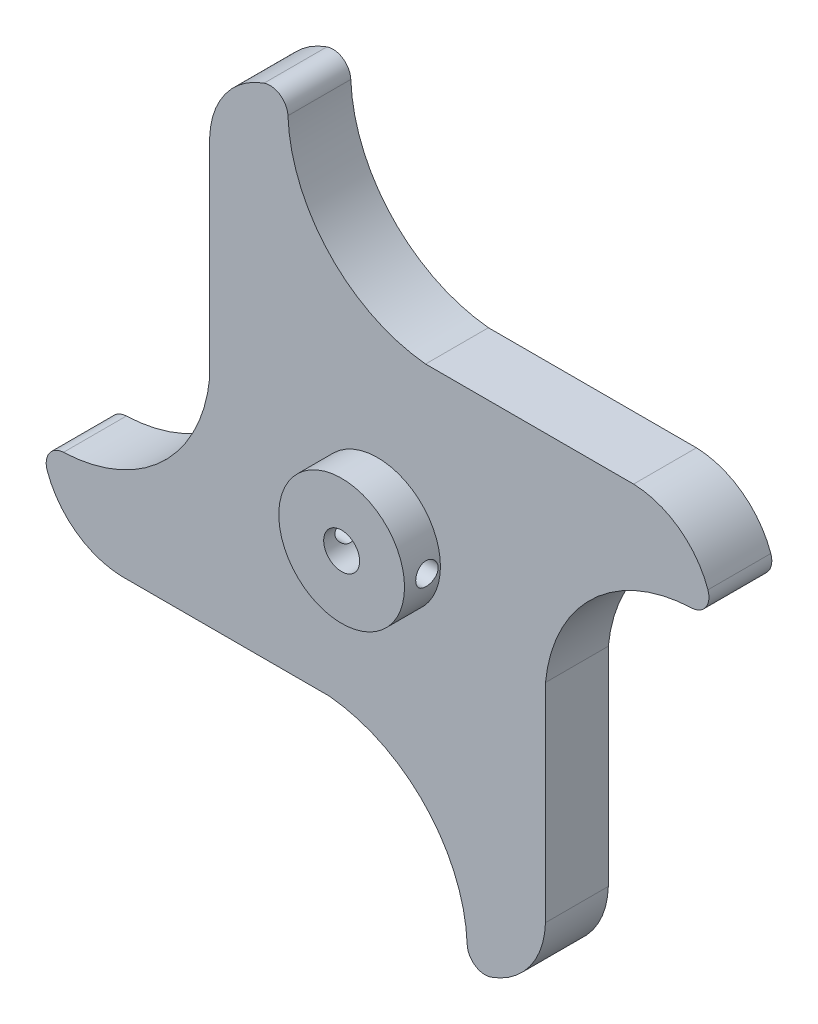
SolidWorks part; units mm, degrees
ref_plane "前视基准面" through (0, 0, 0) normal (0, 0, 1) x (1, 0, 0)
ref_plane "上视基准面" through (0, 0, 0) normal (0, 1, 0) x (1, 0, 0)
ref_plane "右视基准面" through (0, 0, 0) normal (1, 0, 0) x (0, 0, -1)
sketch "草图1" plane through (0, 0, 0) normal (0, 0, 1) x (1, 0, 0)
  circle A0 centre (0, 0) radius 2
  arc A5 (40.8798, 28.7896) -> (28.7896, 40.8798) centre (0, 0) ccw
  arc A7 (-28.7896, 40.8798) -> (-40.8798, 28.7896) centre (0, 0) ccw
  arc A9 (-40.8798, -28.7896) -> (-28.7896, -40.8798) centre (0, 0) ccw
  arc A11 (28.7896, -40.8798) -> (40.8798, -28.7896) centre (0, 0) ccw
  arc A13 (-22.8945, 32.8) -> (22.8945, 32.8) centre (0, 55.6945) ccw
  arc A14 (32.8, 22.8945) -> (32.8, -22.8945) centre (55.6945, 0) ccw
  arc A15 (22.8945, -32.8) -> (-22.8945, -32.8) centre (0, -55.6945) ccw
  arc A16 (-32.8, -22.8945) -> (-32.8, 22.8945) centre (-55.6945, 0) ccw
  arc A21 (-28.7896, 40.8798) -> (28.7896, 40.8798) centre (0, 55.6945) ccw
  arc A22 (40.8798, 28.7896) -> (40.8798, -28.7896) centre (55.6945, 0) ccw
  arc A23 (28.7896, -40.8798) -> (-28.7896, -40.8798) centre (0, -55.6945) ccw
  arc A24 (-40.8798, -28.7896) -> (-40.8798, 28.7896) centre (-55.6945, 0) ccw
  point P13 (45, 0)
  point P16 (0, 0)
  point P45 (0, 0)
  point P47 (0, 0)
  point P63 (0, 0)
  dimension "D1" = 4
  dimension "D3" = 4
  dimension "D4" = 4
extrude "凸台-拉伸1" add sketch "草图1" along normal blind 7 contours A24 A16 A9 A23 A15 A11 A22 A14 A5 A21 A13 A7 A0 region at (35.9294, 27.09, 0)
sketch "草图2" plane through (0, 0, 7) normal (0, 0, 1) x (1, 0, 0)
  line L0 (24.2343, 0) -> (24.2343, 20.8516)
  line L1 (0, -24.2343) -> (-200, -24.2343)
  line L2 (-200, -71.6) -> (3.2733, -71.6)
  line L3 (0, -70) -> (-200, -70)
  line L4 (-200, -23.4) -> (-200, -71.6)
  line L5 (24.2343, 34.0432) -> (24.2343, 20.8516)
  line L6 (-200, -47.5) -> (-20.9464, -47.5)
  line L7 (-200, -23.4) -> (-42.5285, -23.4)
  line L8 (70, 0) -> (70, 107.3223)
  line L9 (24.2343, 34.0432) -> (24.2343, 107.3223)
  line L10 (-35.8334, -17.6395) -> (24.2343, 34.0432)
  line L11 (24.2343, 34.0432) -> (-43.4982, -24.2343)
  line L12 (0, -24.2343) -> (0, 0)
  line L13 (0, 0) -> (0, -24.2343)
  line L14 (-43.4982, -24.2343) -> (-43.4982, -70)
  line L15 (-310.8913, -229.5208) -> (-198.8913, -229.5208)
  line L16 (-254.8913, -229.5208) -> (-251.3913, -229.5208)
  line L17 (-251.3913, -229.5208) -> (-258.3913, -229.5208)
  line L18 (-258.3913, -229.5208) -> (-258.3913, -112.5315)
  line L19 (-258.3913, -112.5315) -> (-251.3913, -112.5315)
  line L20 (-251.3913, -112.5315) -> (-251.3913, -229.5208)
  line L21 (24.2343, 107.3223) -> (70, 107.3223)
  line L22 (47.1172, 107.3223) -> (47.1172, -141.393)
  line L23 (-20.9464, -47.5) -> (114.3656, -47.5)
  line L24 (0, 0) -> (0, -24.2343)
  circle A0 centre (0, -49) radius 21
  circle A1 centre (-310.8913, -229.5208) radius 38.25
  arc A2 (0, -24.2343) -> (24.2343, 0) centre (0, 0) ccw
  arc A3 (0, -70) -> (70, 0) centre (0, 0) ccw
  circle A4 centre (-198.8913, -229.5208) radius 38.25
  circle A5 centre (0, 0) radius 47.1172
  circle A10 centre (-254.8913, -208.9571) radius 21.4063
  point P19 (0, 0)
sketch "草图5" plane through (0, 0, 7) normal (0, 0, 1) x (1, 0, 0)
  line L1 (0, 2.5) -> (-1.7806, 2.5)
  line L2 (-1.7806, 2.5) -> (1.6583, 2.5)
  arc A0 (1.6583, 2.5) -> (-1.6583, 2.5) centre (0, 0) ccw
  circle A1 centre (0, 0) radius 7
  circle M18 centre (0, 0) radius 2
extrude "凸台-拉伸2" add sketch "草图5" along normal blind 4 contours A1 M18 | L1 L2 M18 region at (0, 2.7015, 7) region at (-6.802, 0, 7)
sketch "草图11" plane through (0, 0, 0) normal (1, 0, 0) x (0, 0, -1)
  line L0 (0, 0) -> (-7, 0)
  line L1 (-7, 0) -> (-10, 0)
  circle A0 centre (-8.5, 0) radius 1.25
extrude "切除-拉伸5" cut sketch "草图11" against normal blind 15 and the other way blind 8 contours L1 A0 | L1 A0 region at (0, -0.5305, 8.5) region at (0, 0.5305, 8.5)
sketch "草图13" plane through (0, 0, 0) normal (0, 0, -1) x (-1, 0, 0)
  arc A0 (-25.2436, 31.0284) -> (25.2436, 31.0284) centre (0, 50.6945) ccw
  arc A1 (31.0284, 25.2436) -> (31.0284, -25.2436) centre (50.6945, 0) ccw
  arc A2 (25.2436, -31.0284) -> (-25.2436, -31.0284) centre (0, -50.6945) ccw
  arc A3 (-31.0284, -25.2436) -> (-31.0284, 25.2436) centre (-50.6945, 0) ccw
  arc A4 (-25.2436, 31.0284) -> (-31.0284, 25.2436) centre (0, 0) ccw
  circle A5 centre (0, 0) radius 82.6945
  arc A6 (-31.0284, -25.2436) -> (-25.2436, -31.0284) centre (0, 0) ccw
  arc A7 (25.2436, -31.0284) -> (31.0284, -25.2436) centre (0, 0) ccw
  arc A8 (31.0284, 25.2436) -> (25.2436, 31.0284) centre (0, 0) ccw
  point P14 (0, 0)
  dimension "D1" = 4
extrude "切除-拉伸13" cut sketch "草图13" against normal blind 10
fillet "圆角1" radius 2 4 edges at (-31.0284, -25.2436, 3.5) (31.0284, -25.2436, 3.5) (25.2436, 31.0284, 3.5) (-31.0284, 25.2436, 3.5)
fillet "圆角2" radius 2 4 edges at (-25.2436, -31.0284, 3.5) (25.2436, -31.0284, 3.5) (31.0284, 25.2436, 3.5) (-25.2436, 31.0284, 3.5)
sketch "草图14" plane through (0, 0, 0) normal (0, 0, -1) x (-1, 0, 0)
  line L0 (0, 18.6945) -> (-34.0956, 18.6945)
  line L1 (18.6945, 0) -> (18.6945, 34.0956)
  line L2 (0, -18.6945) -> (34.0956, -18.6945)
  line L3 (-18.6945, 0) -> (-18.6945, -34.0956)
  line L4 (34.0956, -16.9082) -> (34.0956, -18.6945)
  line L5 (-16.9082, -34.0956) -> (-18.6945, -34.0956)
  line L6 (-34.0956, 16.9082) -> (-34.0956, 18.6945)
  line L7 (16.9082, 34.0956) -> (18.6945, 34.0956)
  line L8 (13.8017, 34.0956) -> (18.6945, 34.0956)
  line L9 (34.0956, -13.8017) -> (34.0956, -18.6945)
  line L10 (-13.8017, -34.0956) -> (-18.6945, -34.0956)
  line L11 (-34.0956, 13.8017) -> (-34.0956, 18.6945)
  arc A1 (-23.9852, 29.5117) -> (23.9852, 29.5117) centre (0, 50.6945) ccw construction
  arc A5 (0, 18.6945) -> (13.8017, 34.0956) centre (-0.7997, 33.296) ccw
  arc A6 (18.6945, 0) -> (34.0956, -13.8017) centre (33.296, 0.7997) ccw
  arc A7 (0, -18.6945) -> (-13.8017, -34.0956) centre (0.7997, -33.296) ccw
  arc A8 (-18.6945, 0) -> (-34.0956, 13.8017) centre (-33.296, -0.7997) ccw
  point P22 (0, 0)
  point P29 (0, 0)
  point P35 (0, 0)
  point P41 (0, 0)
  arc M1 (-23.9852, -29.5117) -> (23.9852, -29.5117) centre (0, -50.6945) cw
  arc M5 (29.5117, -23.9852) -> (29.5117, 23.9852) centre (50.6945, 0) cw
  arc M9 (23.9852, 29.5117) -> (-23.9852, 29.5117) centre (0, 50.6945) cw
  arc M13 (-29.5117, 23.9852) -> (-29.5117, -23.9852) centre (-50.6945, 0) cw
  circle M17 centre (0, 0) radius 2
  dimension "D1" = 4
  dimension "D3" = 4
  dimension "D2" = 4
  dimension "D4" = 4
extrude "凸台-拉伸5" add sketch "草图14" against normal up to surface (7 mm away) contours L3 L2 L1 L0 M13 M1 M5 M9 M17 | A8 L0 L6 L11 M13 | A5 L1 L7 L8 M9 | A6 L2 L4 L9 M5 | A7 L3 L5 L10 M1 region at (-10.0359, 19.5734, 0) region at (-14.1137, 26.53, 0) region at (26.53, 14.1137, 0) region at (-26.53, -14.1137, 0) region at (14.1137, -26.53, 0) up to face at (0, 0, 7)
sketch "草图15" plane through (0, 0, 0) normal (0, 0, -1) x (-1, 0, 0)
  line L0 (-24.7231, 18.6945) -> (0, 18.6945)
  line L1 (18.6945, 0) -> (18.6945, 24.7231)
  line L2 (24.7231, -18.6945) -> (0.9271, -18.708)
  line L3 (24.7231, -18.6945) -> (0, -18.6945)
  line L4 (18.6945, 24.7231) -> (18.6945, 0)
  line L5 (24.7231, -18.6945) -> (0, -18.6945)
  line L6 (-18.6945, -24.7231) -> (-18.6945, 0)
  line L7 (-18.6945, -24.7231) -> (-25.6921, -33.3347)
  line L8 (-25.6921, -33.3347) -> (-42.4976, -12.5302)
  line L9 (-42.4976, -12.5302) -> (-18.6945, 0)
  line L10 (-12.5302, 42.4976) -> (0, 18.6945)
  line L11 (-33.3347, 25.6921) -> (-12.5302, 42.4976)
  line L12 (-24.7231, 18.6945) -> (-33.3347, 25.6921)
  line L13 (42.4976, 12.5302) -> (18.6945, 0)
  line L14 (25.6921, 33.3347) -> (42.4976, 12.5302)
  line L15 (18.6945, 24.7231) -> (25.6921, 33.3347)
  line L16 (12.5302, -42.4976) -> (0, -18.6945)
  line L17 (33.3347, -25.6921) -> (12.5302, -42.4976)
  line L18 (24.7231, -18.6945) -> (33.3347, -25.6921)
  arc A0 (-23.9852, 29.5117) -> (0, 18.6945) centre (0, 50.6945) ccw construction
  arc A1 (0, 18.6945) -> (13.8017, 34.0956) centre (-0.7997, 33.296) ccw construction
  arc A2 (18.6945, 24.7231) -> (23.9852, 29.5117) centre (0, 50.6945) ccw construction
  arc A3 (23.9852, -29.5117) -> (0, -18.6945) centre (0, -50.6945) ccw construction
  point P35 (0, 0)
  point P47 (0, 0)
  arc M1 (-23.9852, -29.5117) -> (-18.6945, -24.7231) centre (0, -50.6945) cw
  arc M5 (0, -18.6945) -> (23.9852, -29.5117) centre (0, -50.6945) cw
  arc M6 (23.9852, -29.5117) -> (26.8255, -29.6714) centre (25.4843, -28.1878) ccw
  arc M7 (26.8255, -29.6714) -> (29.6714, -26.8255) centre (0, 0) ccw
  arc M8 (29.6714, -26.8255) -> (29.5117, -23.9852) centre (28.1878, -25.4843) ccw
  arc M9 (29.5117, -23.9852) -> (24.7231, -18.6945) centre (50.6945, 0) cw
  arc M13 (18.6945, 0) -> (29.5117, 23.9852) centre (50.6945, 0) cw
  arc M14 (29.5117, 23.9852) -> (29.6714, 26.8255) centre (28.1878, 25.4843) ccw
  arc M15 (29.6714, 26.8255) -> (26.8255, 29.6714) centre (0, 0) ccw
  arc M16 (26.8255, 29.6714) -> (23.9852, 29.5117) centre (25.4843, 28.1878) ccw
  arc M17 (23.9852, 29.5117) -> (18.6945, 24.7231) centre (0, 50.6945) cw
  arc M21 (0, 18.6945) -> (-23.9852, 29.5117) centre (0, 50.6945) cw
  arc M22 (-23.9852, 29.5117) -> (-26.8255, 29.6714) centre (-25.4843, 28.1878) ccw
  arc M23 (-26.8255, 29.6714) -> (-29.6714, 26.8255) centre (0, 0) ccw
  arc M24 (-29.6714, 26.8255) -> (-29.5117, 23.9852) centre (-28.1878, 25.4843) ccw
  arc M25 (-29.5117, 23.9852) -> (-24.7231, 18.6945) centre (-50.6945, 0) cw
  arc M29 (-18.6945, 0) -> (-29.5117, -23.9852) centre (-50.6945, 0) cw
  arc M30 (-29.5117, -23.9852) -> (-29.6714, -26.8255) centre (-28.1878, -25.4843) ccw
  arc M31 (-29.6714, -26.8255) -> (-26.8255, -29.6714) centre (0, 0) ccw
  arc M32 (-26.8255, -29.6714) -> (-23.9852, -29.5117) centre (-25.4843, -28.1878) ccw
  dimension "D1" = 4
  dimension "D2" = 4
extrude "切除-拉伸14" cut sketch "草图15" against normal blind 10 contours L12 L10 L11 M25 M24 M23 M22 M21 | L0 M25 M21 M22 M23 M24 | L1 M13 M14 M15 M16 M17 | L15 L13 L14 M17 M16 M15 M14 M13 | L2 M9 M5 M6 M7 M8 | L18 L16 L17 M9 M8 M7 M6 M5 | L9 L8 L7 M1 M32 M31 M30 M29 | L6 M1 M29 M30 M31 M32 region at (21.1855, 23.0093, 0) region at (14.0492, 29.1558, 0) region at (-29.1558, 14.0492, 0) region at (-23.0093, 21.1855, 0) region at (-21.2018, -23.0149, 0) region at (-14.0492, -29.1558, 0) region at (23.0093, -21.1855, 0) region at (29.1558, -14.0492, 0)
fillet "圆角3" radius 3 4 edges at (34.0956, 18.6945, 3.5) (18.6945, -34.0956, 3.5) (-34.0956, -18.6945, 3.5) (-18.6945, 34.0956, 3.5)
fillet "圆角4" radius 1 4 edges at (-34.0956, -13.8017, 3.5) (13.8017, -34.0956, 3.5) (34.0956, 13.8017, 3.5) (-13.8017, 34.0956, 3.5)
sketch "草图16" plane through (0, 0, 0) normal (0, 0, -1) x (-1, 0, 0)
  arc A0 (5.3467, -18.6945) -> (-9.9109, -37.2905) centre (7.0159, -35.6213) ccw
  arc A1 (-18.6945, -27.9842) -> (-9.9109, -37.2905) centre (-9.6496, -28.2455) ccw
  arc A2 (-18.6945, -5.3467) -> (-37.2905, 9.9109) centre (-35.6213, -7.0159) ccw
  arc A3 (-27.9842, 18.6945) -> (-37.2905, 9.9109) centre (-28.2455, 9.6496) ccw
  arc A4 (-5.3467, 18.6945) -> (9.9109, 37.2905) centre (-7.0159, 35.6213) ccw
  arc A5 (27.9842, -18.6945) -> (37.2905, -9.9109) centre (28.2455, -9.6496) ccw
  arc A6 (18.6945, 27.9842) -> (9.9109, 37.2905) centre (9.6496, 28.2455) ccw
  arc A9 (18.6945, 5.3467) -> (37.2905, -9.9109) centre (35.6213, 7.0159) ccw
  point P21 (0, 0)
  line M3 (34.0956, -15.6945) -> (34.0956, -14.8223)
  arc M4 (34.0956, -14.8223) -> (33.1085, -13.8224) centre (33.0956, -14.8223) ccw
  arc M5 (33.1085, -13.8224) -> (18.6945, 0) centre (33.296, 0.7997) cw
  line M6 (18.6945, 0) -> (18.6945, 31.0956)
  arc M7 (18.6945, 31.0956) -> (15.6945, 34.0956) centre (15.6945, 31.0956) ccw
  line M8 (15.6945, 34.0956) -> (14.8223, 34.0956)
  arc M9 (14.8223, 34.0956) -> (13.8224, 33.1085) centre (14.8223, 33.0956) ccw
  arc M10 (13.8224, 33.1085) -> (0, 18.6945) centre (-0.7997, 33.296) cw
  line M11 (0, 18.6945) -> (-31.0956, 18.6945)
  arc M12 (-31.0956, 18.6945) -> (-34.0956, 15.6945) centre (-31.0956, 15.6945) ccw
  line M13 (-34.0956, 15.6945) -> (-34.0956, 14.8223)
  arc M14 (-34.0956, 14.8223) -> (-33.1085, 13.8224) centre (-33.0956, 14.8223) ccw
  arc M15 (-33.1085, 13.8224) -> (-18.6945, 0) centre (-33.296, -0.7997) cw
  line M16 (-18.6945, 0) -> (-18.6945, -31.0956)
  arc M17 (-18.6945, -31.0956) -> (-15.6945, -34.0956) centre (-15.6945, -31.0956) ccw
  line M18 (-15.6945, -34.0956) -> (-14.8223, -34.0956)
  arc M19 (-14.8223, -34.0956) -> (-13.8224, -33.1085) centre (-14.8223, -33.0956) ccw
  arc M20 (-13.8224, -33.1085) -> (0, -18.6945) centre (0.7997, -33.296) cw
  arc M21 (0, -18.6945) -> (0.9271, -18.708) centre (0, -50.6945) cw
  line M22 (0.9271, -18.708) -> (24.7231, -18.6945)
  arc M24 (31.0956, -18.6945) -> (34.0956, -15.6945) centre (31.0956, -15.6945) ccw
  dimension "D1" = 4
sketch "草图17" plane through (0, 0, 7) normal (0, 0, 1) x (1, 0, 0)
  arc A0 (-18.6945, 27.9842) -> (-9.9109, 37.2905) centre (-9.6496, 28.2455) cw
  arc A1 (-9.9109, 37.2905) -> (5.3467, 18.6945) centre (7.0159, 35.6213) ccw
  arc A2 (37.2905, 9.9109) -> (18.6945, -5.3467) centre (35.6213, -7.0159) ccw
  arc A3 (27.9842, 18.6945) -> (37.2905, 9.9109) centre (28.2455, 9.6496) cw
  arc A4 (9.9109, -37.2905) -> (-5.3467, -18.6945) centre (-7.0159, -35.6213) ccw
  arc A5 (18.6945, -27.9842) -> (9.9109, -37.2905) centre (9.6496, -28.2455) cw
  arc A6 (-37.2905, -9.9109) -> (-18.6945, 5.3467) centre (-35.6213, 7.0159) ccw
  arc A7 (-27.9842, -18.6945) -> (-37.2905, -9.9109) centre (-28.2455, -9.6496) cw
  point P26 (0, 0)
  dimension "D1" = 4
extrude "凸台-拉伸6" add sketch "草图16" against normal up to surface (7 mm away) contours A6 A4 M7 M11 M10 M9 M8 | A3 A2 M12 M16 M15 M14 M13 | A1 A0 M17 M22 M21 M20 M19 M18 | A9 A5 M6 M5 M4 M3 M24 region at (-27.4674, -8.8381, 0) region at (-8.8381, 27.4674, 0) region at (27.4674, 8.8381, 0) region at (8.8457, -27.4731, 0) up to face at (-1.1659, -1.7, 7)
sketch "草图18" plane through (0, 0, 7) normal (0, 0, 1) x (1, 0, 0)
  line L0 (5.3467, 18.6945) -> (27.9842, 18.6945)
  line L1 (18.6945, -5.3467) -> (18.6945, -27.9842)
  line L2 (-5.3467, -18.6945) -> (-27.9842, -18.6945)
  line L3 (-18.6945, 5.3467) -> (-18.6945, 27.9842)
  arc A0 (-18.6945, 27.9842) -> (-9.9109, 37.2905) centre (-9.6496, 28.2455) cw
  arc A1 (-9.9109, 37.2905) -> (5.3467, 18.6945) centre (7.0159, 35.6213) ccw
  arc A2 (27.9842, 18.6945) -> (37.2905, 9.9109) centre (28.2455, 9.6496) cw
  arc A3 (37.2905, 9.9109) -> (18.6945, -5.3467) centre (35.6213, -7.0159) ccw
  arc A4 (18.6945, -27.9842) -> (9.9109, -37.2905) centre (9.6496, -28.2455) cw
  arc A5 (9.9109, -37.2905) -> (-5.3467, -18.6945) centre (-7.0159, -35.6213) ccw
  arc A6 (-27.9842, -18.6945) -> (-37.2905, -9.9109) centre (-28.2455, -9.6496) cw
  arc A7 (-37.2905, -9.9109) -> (-18.6945, 5.3467) centre (-35.6213, 7.0159) ccw
  circle A8 centre (0, 0) radius 47.2388
  point P31 (0, 0)
  dimension "D1" = 4
extrude "切除-拉伸15" cut sketch "草图18" against normal blind 10
fillet "圆角5" radius 2 4 edges at (-37.2905, -9.9109, 3.5) (9.9109, -37.2905, 3.5) (37.2905, 9.9109, 3.5) (-9.9109, 37.2905, 3.5)
sketch "草图19" plane through (0, 0, 7) normal (0, 0, 1) x (1, 0, 0)
  circle A0 centre (0, 0) radius 9.5
  circle A1 centre (9.5, 0) radius 3
extrude "切除-拉伸16" [suppressed] cut sketch "草图19" against normal blind 10 contours A0 A1 | A0 A1
ref_plane "基准面1" through (0, 0, 3.5) normal (0, 0, -1) x (-1, 0, 0)
